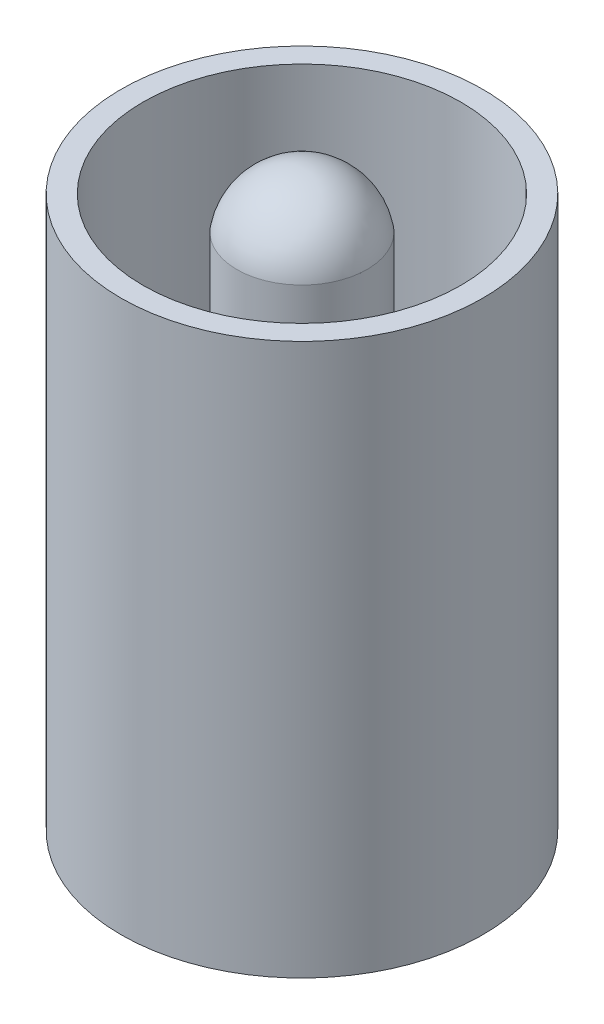
SolidWorks part; units mm, degrees
ref_plane "Front Plane" through (0, 0, 0) normal (0, 0, 1) x (1, 0, 0)
ref_plane "Top Plane" through (0, 0, 0) normal (0, 1, 0) x (1, 0, 0)
ref_plane "Right Plane" through (0, 0, 0) normal (1, 0, 0) x (0, 0, -1)
sketch "Sketch1" plane through (0, 0, 0) normal (0, 1, 0) x (1, 0, 0)
  circle A0 centre (0, 0) radius 4.1672
  dimension "D1" = 8.3344
extrude "Boss-Extrude1" add sketch "Sketch1" along normal blind 12.7
shell "Shell1" thickness 0.508 removed face at (0, 12.7, 4.1672)
sketch "Sketch2" plane through (0, 0.508, 0) normal (0, 1, 0) x (1, 0, 0)
  circle A0 centre (0, 0) radius 1.5
  dimension "D1" = 3
extrude "Boss-Extrude2" add sketch "Sketch2" along normal blind 11.43
dome "Dome1" faces to dome 1 distance 1.27 reverse direction no elliptical dome no face at (0, 11.938, 1.5) parameters "D1"=1.27
